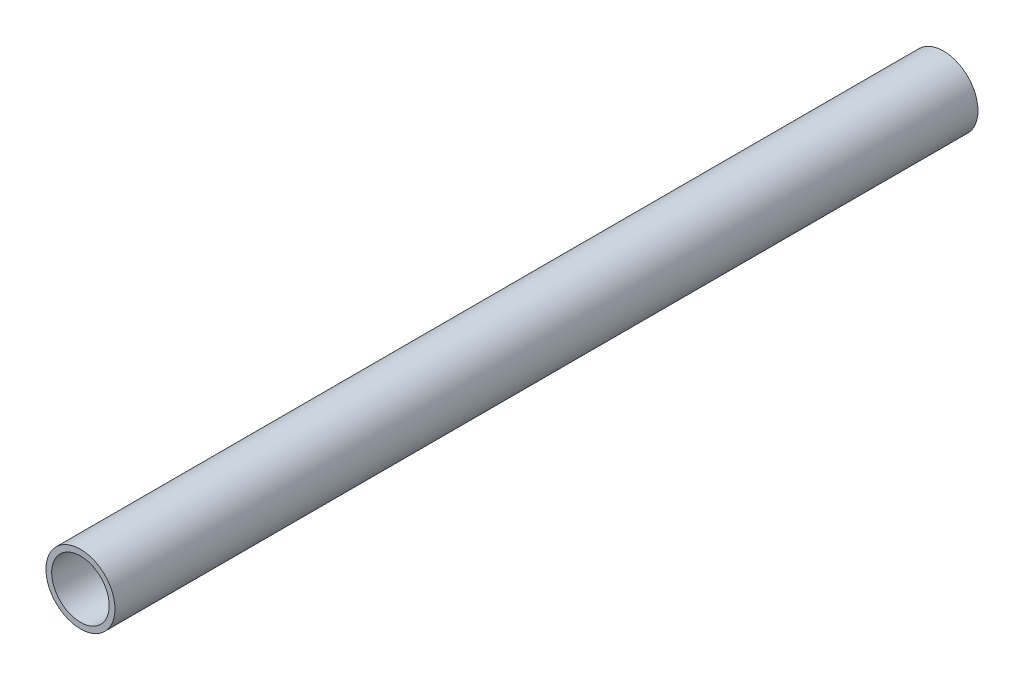
SolidWorks part; units mm, degrees
ref_plane "Alzado" through (0, 0, 0) normal (0, 0, 1) x (1, 0, 0)
ref_plane "Planta" through (0, 0, 0) normal (0, 1, 0) x (1, 0, 0)
ref_plane "Vista lateral" through (0, 0, 0) normal (1, 0, 0) x (0, 0, -1)
sketch "Croquis1" plane through (0, 0, 0) normal (0, 0, 1) x (1, 0, 0)
  circle A0 centre (0, 0) radius 6
  circle A1 centre (0, 0) radius 5
  dimension "D1" = 12
  dimension "D2" = 1
extrude "Saliente-Extruir1" add sketch "Croquis1" along normal mid plane 150
